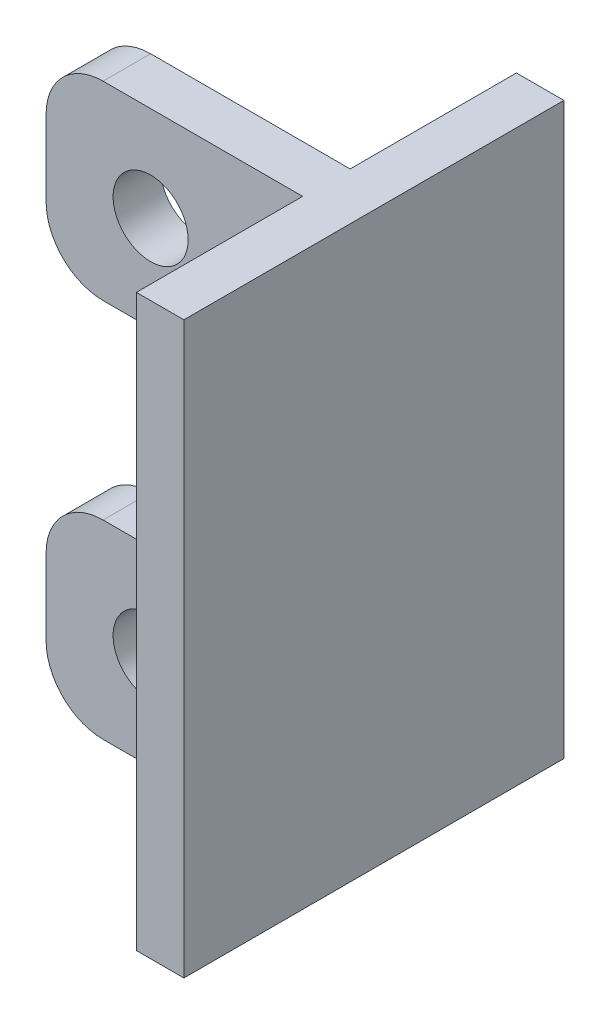
SolidWorks part; units mm, degrees
ref_plane "Alzado" through (0, 0, 0) normal (0, 0, 1) x (1, 0, 0)
ref_plane "Planta" through (0, 0, 0) normal (0, 1, 0) x (1, 0, 0)
ref_plane "Vista lateral" through (0, 0, 0) normal (1, 0, 0) x (0, 0, -1)
sketch "Croquis1" plane through (0, 0, 0) normal (0, 0, 1) x (1, 0, 0)
  line L0 (0, 12.7) -> (0, -12.7) construction
  line L1 (13.335, 19.05) -> (-3.175, 19.05)
  line L2 (-4.445, -4.445) -> (4.445, -4.445) construction
  line L3 (-4.445, -4.445) -> (-4.445, 4.445) construction
  line L4 (-4.445, 4.445) -> (4.445, 4.445) construction
  line L5 (4.445, -4.445) -> (4.445, 4.445) construction
  line L6 (-4.445, -4.445) -> (4.445, 4.445) construction
  line L7 (-4.445, 4.445) -> (4.445, -4.445) construction
  line L8 (-6.985, 15.24) -> (-6.985, 10.16)
  line L9 (-3.175, 6.35) -> (3.175, 6.35)
  line L10 (6.985, 2.54) -> (6.985, -2.54)
  line L11 (3.175, -6.35) -> (-3.175, -6.35)
  line L12 (-6.985, -10.16) -> (-6.985, -15.24)
  line L13 (-3.175, -19.05) -> (13.335, -19.05)
  line L14 (-2.5082, -12.7) -> (2.5083, -12.7) construction
  line L15 (-2.5083, 12.7) -> (2.5082, 12.7) construction
  line L16 (13.335, 19.05) -> (13.335, -19.05)
  circle A0 centre (0, 12.7) radius 2.5083
  circle A1 centre (0, -12.7) radius 2.5083
  arc A2 (-6.985, -15.24) -> (-3.175, -19.05) centre (-3.175, -15.24) ccw
  arc A3 (-3.175, -6.35) -> (-6.985, -10.16) centre (-3.175, -10.16) ccw
  arc A4 (-6.985, 10.16) -> (-3.175, 6.35) centre (-3.175, 10.16) ccw
  arc A5 (-3.175, 19.05) -> (-6.985, 15.24) centre (-3.175, 15.24) ccw
  arc A6 (6.985, -2.54) -> (3.175, -6.35) centre (3.175, -2.54) cw
  arc A7 (3.175, 6.35) -> (6.985, 2.54) centre (3.175, 2.54) cw
  point P4 (0, 0)
  point P7 (0, 0)
  point P20 (6.985, 0)
  point P37 (6.985, 3.205)
  dimension "D1" = 5.0165
  dimension "D8" = 3.81
  dimension "D4" = 3.81
  dimension "D2" = 25.4
  dimension "D3" = 8.89
  dimension "D5" = 20.32
  dimension "D6" = 2.54
  dimension "D7" = 2.54
  dimension "D9" = 12.7
  dimension "D10" = 6.35
extrude "Saliente-Extruir1" add sketch "Croquis1" along normal mid plane 3.175
sketch "Croquis2" plane through (0, 0, 0) normal (0, 0, 1) x (1, 0, 0)
  line L0 (-3.175, -19.05) -> (13.335, -19.05) construction
  line L1 (13.335, 19.05) -> (10.16, 19.05)
  line L2 (13.335, 19.05) -> (13.335, -19.05)
  line L3 (13.335, -19.05) -> (10.16, -19.05)
  line L4 (10.16, 19.05) -> (10.16, -19.05)
  dimension "D1" = 3.175
extrude "Saliente-Extruir2" add sketch "Croquis2" along normal mid plane 25.4
